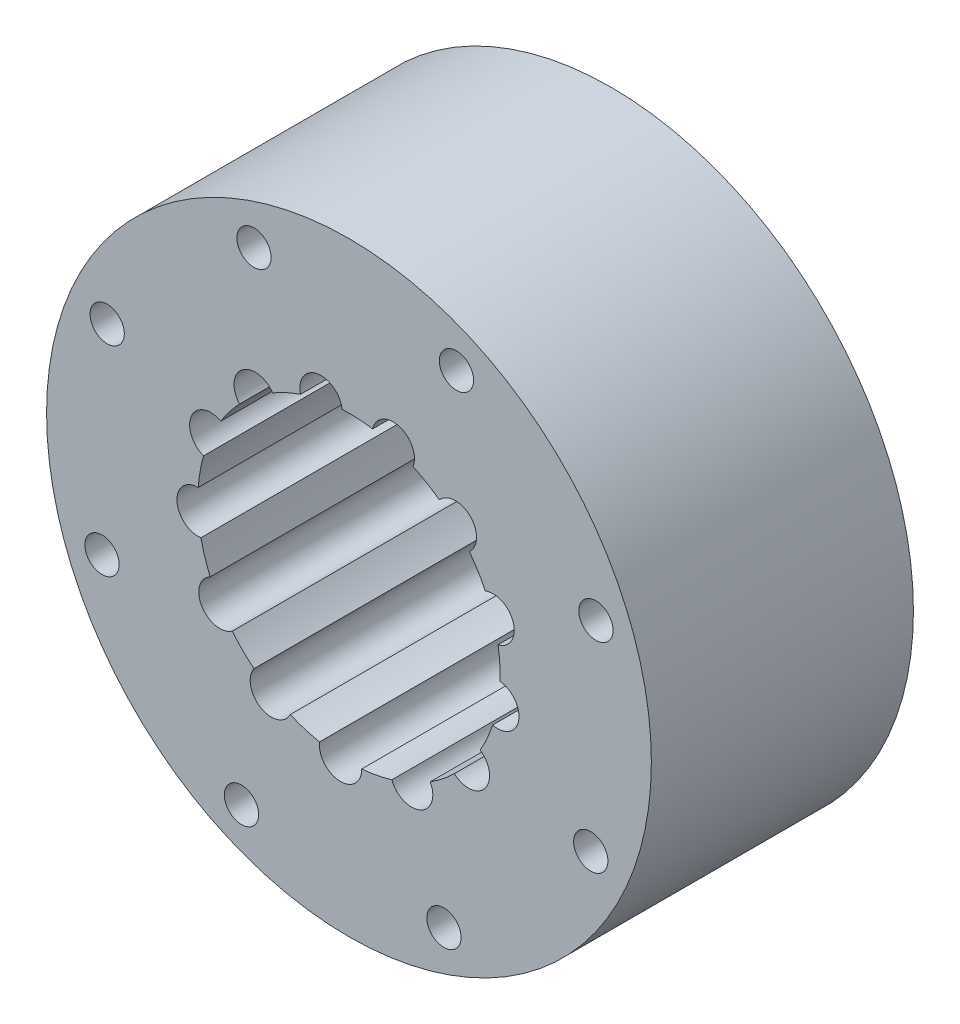
SolidWorks part; units mm, degrees
material "Polylactic Acid (PLA)"
ref_plane "Front Plane" through (0, 0, 0) normal (0, 0, 1) x (1, 0, 0)
ref_plane "Top Plane" through (0, 0, 0) normal (0, 1, 0) x (1, 0, 0)
ref_plane "Right Plane" through (0, 0, 0) normal (1, 0, 0) x (0, 0, -1)
sketch "Sketch2" plane through (0, 0, 0) normal (0, 0, 1) x (1, 0, 0)
  circle A0 centre (0, 0) radius 60
  circle A1 centre (0, 0) radius 45
  dimension "D1" = 120
  dimension "D2" = 15
extrude "Boss-Extrude2" add sketch "Sketch2" along normal mid plane 50
sketch "Sketch3" plane through (0, 0, 25) normal (0, 0, 1) x (1, 0, 0)
  circle A0 centre (0, 0) radius 60
  circle A1 centre (0, 0) radius 60 construction
  arc A2 (29.98, -1.0952) -> (29.5847, 4.9743) centre (0, 0) ccw
  arc A3 (8.504, -28.7695) -> (16.1293, -25.2952) centre (12.4385, -27.2999) ccw
  arc A4 (-5.8399, -29.4261) -> (2.5265, -29.8934) centre (-1.6731, -29.9533) ccw
  arc A5 (-18.846, -23.3416) -> (-11.6551, -27.6434) centre (-15.4015, -25.7448) ccw
  arc A6 (-27.5346, -11.9098) -> (-23.1666, -19.0607) centre (-25.6015, -15.6385) ccw
  arc A7 (-29.9155, 2.2504) -> (-29.3709, -6.1113) centre (-29.9366, -1.9496) ccw
  arc A8 (-25.443, 15.895) -> (-28.8467, 8.2381) centre (-27.4135, 12.186) ccw
  arc A9 (-15.1419, 25.8983) -> (-21.7141, 20.7002) centre (-18.6104, 23.5298) ccw
  arc A10 (-1.3719, 29.9686) -> (-9.607, 28.4202) centre (-5.5438, 29.4833) ccw
  arc A11 (12.7123, 27.1735) -> (4.7009, 29.6294) centre (8.7928, 28.6825) ccw
  arc A12 (23.8843, 18.1532) -> (17.9319, 24.0509) centre (21.115, 21.3109) ccw
  arc A13 (29.5847, 4.9743) -> (27.0549, 12.9627) centre (28.6001, 9.0572) ccw
  arc A14 (28.5076, -9.3442) -> (29.98, -1.0952) centre (29.5332, -5.2714) ccw
  arc A15 (20.8998, -21.5221) -> (26.037, -14.9022) centre (23.7007, -18.3924) ccw
  arc A16 (26.037, -14.9022) -> (28.5076, -9.3442) centre (0, 0) ccw
  arc A17 (16.1293, -25.2952) -> (20.8998, -21.5221) centre (0, 0) ccw
  arc A18 (2.5265, -29.8934) -> (8.504, -28.7695) centre (0, 0) ccw
  arc A19 (-11.6551, -27.6434) -> (-5.8399, -29.4261) centre (0, 0) ccw
  arc A20 (-23.1666, -19.0607) -> (-18.846, -23.3416) centre (0, 0) ccw
  arc A21 (-29.3709, -6.1113) -> (-27.5346, -11.9098) centre (0, 0) ccw
  arc A22 (-28.8467, 8.2381) -> (-29.9155, 2.2504) centre (0, 0) ccw
  arc A23 (-21.7141, 20.7002) -> (-25.443, 15.895) centre (0, 0) ccw
  arc A24 (-9.607, 28.4202) -> (-15.1419, 25.8983) centre (0, 0) ccw
  arc A25 (4.7009, 29.6294) -> (-1.3719, 29.9686) centre (0, 0) ccw
  arc A26 (17.9319, 24.0509) -> (12.7123, 27.1735) centre (0, 0) ccw
  arc A27 (27.0549, 12.9627) -> (23.8843, 18.1532) centre (0, 0) ccw
  point P10 (0, 0)
  point P11 (-29.5086, 5.4076)
  point P35 (0, 0)
  dimension "D1" = 60
  dimension "D2" = 8.4
  dimension "D3" = 13
extrude "Boss-Extrude3" add sketch "Sketch3" along normal blind 2
sketch "Sketch4" plane through (0, 0, 25) normal (0, 0, -1) x (-1, 0, 0)
  arc A0 (-12.7123, 27.1735) -> (-17.9319, 24.0509) centre (0, 0) ccw construction
  circle A1 centre (0, 0) radius 45
  circle A2 centre (0, 0) radius 45
  arc A3 (-4.7009, 29.6294) -> (-12.7123, 27.1735) centre (-8.7928, 28.6825) ccw construction
  arc A4 (1.3719, 29.9686) -> (-4.7009, 29.6294) centre (0, 0) ccw construction
  arc A5 (9.607, 28.4202) -> (1.3719, 29.9686) centre (5.5438, 29.4833) ccw construction
  arc A6 (15.1419, 25.8983) -> (9.607, 28.4202) centre (0, 0) ccw construction
  arc A7 (21.7141, 20.7002) -> (15.1419, 25.8983) centre (18.6104, 23.5298) ccw construction
  arc A8 (25.443, 15.895) -> (21.7141, 20.7002) centre (0, 0) ccw construction
  arc A9 (28.8467, 8.2381) -> (25.443, 15.895) centre (27.4135, 12.186) ccw construction
  arc A10 (29.9155, 2.2504) -> (28.8467, 8.2381) centre (0, 0) ccw construction
  arc A11 (29.3709, -6.1113) -> (29.9155, 2.2504) centre (29.9366, -1.9496) ccw construction
  arc A12 (27.5346, -11.9098) -> (29.3709, -6.1113) centre (0, 0) ccw construction
  arc A13 (23.1666, -19.0607) -> (27.5346, -11.9098) centre (25.6015, -15.6385) ccw construction
  arc A14 (18.846, -23.3416) -> (23.1666, -19.0607) centre (0, 0) ccw construction
  arc A15 (11.6551, -27.6434) -> (18.846, -23.3416) centre (15.4015, -25.7448) ccw construction
  arc A16 (5.8399, -29.4261) -> (11.6551, -27.6434) centre (0, 0) ccw construction
  arc A17 (-2.5265, -29.8934) -> (5.8399, -29.4261) centre (1.6731, -29.9533) ccw construction
  arc A18 (-8.504, -28.7695) -> (-2.5265, -29.8934) centre (0, 0) ccw construction
  arc A19 (-16.1293, -25.2952) -> (-8.504, -28.7695) centre (-12.4385, -27.2999) ccw construction
  arc A20 (-20.8998, -21.5221) -> (-16.1293, -25.2952) centre (0, 0) ccw construction
  arc A21 (-26.037, -14.9022) -> (-20.8998, -21.5221) centre (-23.7007, -18.3924) ccw construction
  arc A22 (-28.5076, -9.3442) -> (-26.037, -14.9022) centre (0, 0) ccw construction
  arc A23 (-29.98, -1.0952) -> (-28.5076, -9.3442) centre (-29.5332, -5.2714) ccw construction
  arc A24 (-29.5847, 4.9743) -> (-29.98, -1.0952) centre (0, 0) ccw construction
  arc A25 (-27.0549, 12.9627) -> (-29.5847, 4.9743) centre (-28.6001, 9.0572) ccw construction
  arc A26 (-23.8843, 18.1532) -> (-27.0549, 12.9627) centre (0, 0) ccw construction
  arc A27 (-17.9319, 24.0509) -> (-23.8843, 18.1532) centre (-21.115, 21.3109) ccw construction
  arc A28 (-12.7123, 27.1735) -> (-17.9319, 24.0509) centre (0, 0) ccw
  arc A29 (-4.7009, 29.6294) -> (-12.7123, 27.1735) centre (-8.7928, 28.6825) ccw
  arc A30 (1.3719, 29.9686) -> (-4.7009, 29.6294) centre (0, 0) ccw
  arc A31 (9.607, 28.4202) -> (1.3719, 29.9686) centre (5.5438, 29.4833) ccw
  arc A32 (15.1419, 25.8983) -> (9.607, 28.4202) centre (0, 0) ccw
  arc A33 (21.7141, 20.7002) -> (15.1419, 25.8983) centre (18.6104, 23.5298) ccw
  arc A34 (25.443, 15.895) -> (21.7141, 20.7002) centre (0, 0) ccw
  arc A35 (28.8467, 8.2381) -> (25.443, 15.895) centre (27.4135, 12.186) ccw
  arc A36 (29.9155, 2.2504) -> (28.8467, 8.2381) centre (0, 0) ccw
  arc A37 (29.3709, -6.1113) -> (29.9155, 2.2504) centre (29.9366, -1.9496) ccw
  arc A38 (27.5346, -11.9098) -> (29.3709, -6.1113) centre (0, 0) ccw
  arc A39 (23.1666, -19.0607) -> (27.5346, -11.9098) centre (25.6015, -15.6385) ccw
  arc A40 (18.846, -23.3416) -> (23.1666, -19.0607) centre (0, 0) ccw
  arc A41 (11.6551, -27.6434) -> (18.846, -23.3416) centre (15.4015, -25.7448) ccw
  arc A42 (5.8399, -29.4261) -> (11.6551, -27.6434) centre (0, 0) ccw
  arc A43 (-2.5265, -29.8934) -> (5.8399, -29.4261) centre (1.6731, -29.9533) ccw
  arc A44 (-8.504, -28.7695) -> (-2.5265, -29.8934) centre (0, 0) ccw
  arc A45 (-16.1293, -25.2952) -> (-8.504, -28.7695) centre (-12.4385, -27.2999) ccw
  arc A46 (-20.8998, -21.5221) -> (-16.1293, -25.2952) centre (0, 0) ccw
  arc A47 (-26.037, -14.9022) -> (-20.8998, -21.5221) centre (-23.7007, -18.3924) ccw
  arc A48 (-28.5076, -9.3442) -> (-26.037, -14.9022) centre (0, 0) ccw
  arc A49 (-29.98, -1.0952) -> (-28.5076, -9.3442) centre (-29.5332, -5.2714) ccw
  arc A50 (-29.5847, 4.9743) -> (-29.98, -1.0952) centre (0, 0) ccw
  arc A51 (-27.0549, 12.9627) -> (-29.5847, 4.9743) centre (-28.6001, 9.0572) ccw
  arc A52 (-23.8843, 18.1532) -> (-27.0549, 12.9627) centre (0, 0) ccw
  arc A53 (-17.9319, 24.0509) -> (-23.8843, 18.1532) centre (-21.115, 21.3109) ccw
  dimension "D1" = 0
extrude "Extrude-Thin1" add sketch "Sketch4" along normal up to surface (50 mm away) thin up to face at (60, 0, -25) thin type one direction wall 2
sketch "Sketch5" plane through (0, 0, 27) normal (0, 0, 1) x (1, 0, 0)
  circle A0 centre (0, 0) radius 52.5
  point P3 (49.0019, 18.8432)
  point P4 (47.9737, -21.3254)
  point P8 (18.8432, -49.0019)
  point P9 (-21.3254, -47.9737)
  point P10 (-49.0019, -18.8432)
  point P11 (-47.9737, 21.3254)
  point P12 (-18.8432, 49.0019)
  point P13 (21.3254, 47.9737)
  point P14 (0, 0)
  dimension "D1" = 105
  dimension "D2" = 8
hole_wizard "Ø6.0mm Dowel Hole1" positions "Sketch5" profile "Sketch6" hole size "Ø6.0" standard "ISO" end condition through all
sketch "Sketch6" plane through (21.3254, 47.9737, 27) normal (1, 0, 0) x (0, -1, 0)
  line L0 (0, 0) -> (0, 52)
  line L1 (0, 52) -> (3.4, 52)
  line L2 (3.4, 52) -> (3.4, 0)
  line L5 (3.4, 0) -> (0, 0)
  line L11 (0, -6.35) -> (0, 107.95) construction
  dimension "Thru Hole Dia." = 6.8
  dimension "Thru Hole Depth" = 52
